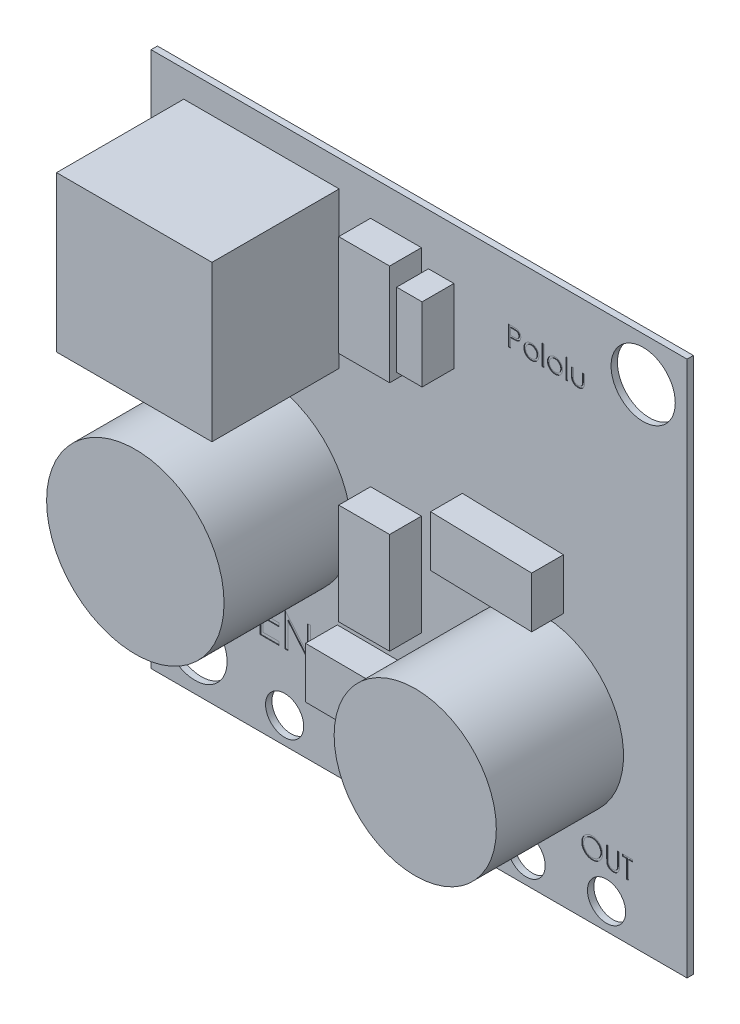
SolidWorks part; units mm, degrees
ref_plane "Front Plane" through (0, 0, 0) normal (0, 0, 1) x (1, 0, 0)
ref_plane "Top Plane" through (0, 0, 0) normal (0, 1, 0) x (1, 0, 0)
ref_plane "Right Plane" through (0, 0, 0) normal (1, 0, 0) x (0, 0, -1)
sketch "Sketch1" plane through (0, 0, 0) normal (0, 0, 1) x (1, 0, 0)
  line L0 (0.669, -0.5811) -> (0.669, 1.1715) construction
  line L1 (-1.0836, -0.5811) -> (20.32, -0.5811)
  line L2 (-1.0836, -0.5811) -> (-1.0836, 20.8225)
  line L3 (-1.0836, 20.8225) -> (20.32, 20.8225)
  line L4 (20.32, -0.5811) -> (20.32, 20.8225)
  line L5 (0.669, 1.1715) -> (-1.0836, 1.1715) construction
  line L6 (18.5674, 20.8225) -> (18.5674, 19.0699) construction
  line L7 (18.5674, 19.0699) -> (20.32, 19.0699) construction
  line L8 (-1.0836, 0.4655) -> (4.2504, 0.4655) construction
  line L9 (4.2504, 0.4655) -> (7.4643, 0.4655) construction
  line L10 (7.4643, 0.4655) -> (10.6782, 0.4655) construction
  line L11 (10.6782, 0.4655) -> (13.8921, 0.4655) construction
  line L12 (13.8921, 0.4655) -> (17.1061, 0.4655) construction
  line L13 (17.1061, 0.4655) -> (20.32, 0.4655) construction
  circle A0 centre (0.669, 1.1715) radius 1.2827
  circle A1 centre (18.5674, 19.0699) radius 1.2827
  circle A2 centre (4.2504, 0.4655) radius 0.762
  circle A3 centre (7.4643, 0.4655) radius 0.762
  circle A4 centre (10.6782, 0.4655) radius 0.762
  circle A5 centre (13.8921, 0.4655) radius 0.762
  circle A6 centre (17.1061, 0.4655) radius 0.762
extrude "Boss-Extrude2" add sketch "Sketch1" along normal blind 0.254
sketch "Sketch2" plane through (0, 0, 0.254) normal (0, 0, 1) x (1, 0, 0)
  line L0 (20.32, 20.8225) -> (-1.0836, 20.8225) construction
  line L1 (0.2217, 19.7636) -> (6.428, 19.7636)
  line L2 (0.2217, 19.7636) -> (0.2217, 13.5573)
  line L3 (0.2217, 13.5573) -> (6.428, 13.5573)
  line L4 (6.428, 19.7636) -> (6.428, 13.5573)
  circle A0 centre (3.3674, 8.2222) radius 3.5433
  circle A1 centre (14.5452, 5.8421) radius 3.2385
extrude "Boss-Extrude3" add sketch "Sketch2" along normal blind 5.08
sketch "Sketch3" plane through (0, 0, 0.254) normal (0, 0, 1) x (1, 0, 0)
  line L1 (6.3544, 4.6463) -> (10.3929, 4.6203)
  line L2 (6.3544, 4.6463) -> (6.3545, 2.6143)
  line L3 (6.3545, 2.6143) -> (10.393, 2.5883)
  line L4 (10.3929, 4.6203) -> (10.393, 2.5883)
  line L5 (7.6807, 10.0893) -> (9.7127, 10.0893)
  line L6 (7.6807, 10.0893) -> (7.6807, 6.0507)
  line L7 (7.6807, 6.0507) -> (9.7127, 6.0507)
  line L8 (9.7127, 10.0893) -> (9.7127, 6.0507)
  line L9 (7.6807, 19.3736) -> (9.7127, 19.3736)
  line L10 (7.6807, 19.3736) -> (7.6807, 15.335)
  line L11 (7.6807, 15.335) -> (9.7127, 15.335)
  line L12 (9.7127, 19.3736) -> (9.7127, 15.335)
  line L13 (11.3476, 11.6941) -> (15.3849, 11.59)
  line L14 (11.3476, 11.6941) -> (11.3498, 9.6621)
  line L15 (11.3498, 9.6621) -> (15.3871, 9.558)
  line L16 (15.3849, 11.59) -> (15.3871, 9.558)
  line L17 (9.9933, 18.7829) -> (11.0093, 18.7829)
  line L18 (9.9933, 18.7829) -> (9.9933, 15.8365)
  line L19 (9.9933, 15.8365) -> (11.0093, 15.8365)
  line L20 (11.0093, 18.7829) -> (11.0093, 15.8365)
extrude "Boss-Extrude4" add sketch "Sketch3" along normal blind 1.27
sketch "Sketch4" plane through (0, 0, 0.254) normal (0, 0, 1) x (1, 0, 0)
  line L0 (13.09, 17.6755) -> (16.0548, 17.6755) construction
  line L1 (3.1036, 2.7739) -> (4.2739, 2.7739) construction
  line L2 (7.0305, 1.6296) -> (8.0968, 1.6296) construction
  line L3 (10.3594, 1.6296) -> (12.3098, 1.6296) construction
  line L4 (16.0548, 1.6296) -> (18.4734, 1.6296) construction
  text T0 "Pololu" font "Century Gothic" height in points 3
  text T1 "EN" font "Century Gothic" height in points 5
  text T2 "VIN" font "Century Gothic" height in points 3
  text T3 "GND" font "Century Gothic" height in points 3
  text T4 "OUT" font "Century Gothic" height in points 3
extrude "Cut-Extrude1" cut sketch "Sketch4" against normal blind 0.0254
